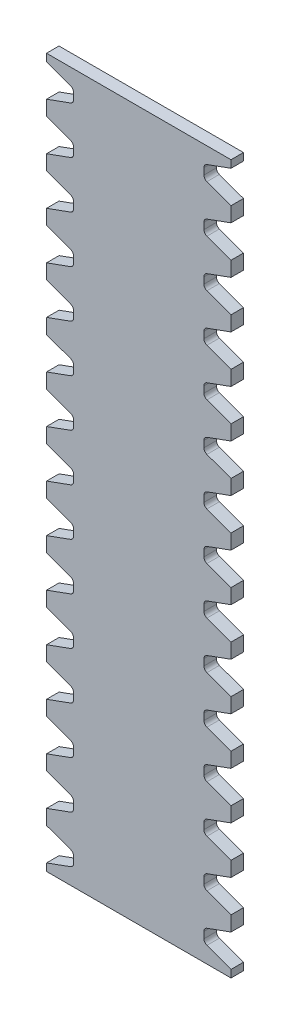
SolidWorks part; units mm, degrees
ref_plane "Front Plane" through (0, 0, 0) normal (0, 0, 1) x (1, 0, 0)
ref_plane "Top Plane" through (0, 0, 0) normal (0, 1, 0) x (1, 0, 0)
ref_plane "Right Plane" through (0, 0, 0) normal (1, 0, 0) x (0, 0, -1)
ref_axis "Axis1" through (0, -55, 0) along (0, 1, 0)
sketch "SketchCI.m_strSketchName" plane through (0, 0, 0) normal (0, 0, 1) x (1, 0, 0)
  line L0 (-7.7057, 15.1301) -> (-7.7057, -438.7728)
  line L1 (-7.7057, -438.7728) -> (51.376, -438.7728)
  line L2 (51.376, -438.7728) -> (51.376, 15.1301)
  line L3 (51.376, 15.1301) -> (-7.7057, 15.1301)
  dimension "D1" = 7.7057
  dimension "D2" = 438.7728
  dimension "D3" = 51.376
  dimension "D4" = 15.1301
extrude "ExtrudeCI" add sketch "SketchCI.m_strSketchName" along normal blind 4 and the other way blind 4
sketch "SketchToothGeartrax1Gear" plane through (0, 0, 0) normal (0, 0, 1) x (1, 0, 0)
  line L0 (-7.7057, 10.3697) -> (-7.7057, -10.3697)
  line L1 (-7.7057, -10.3697) -> (7.7308, -4.7513)
  line L2 (9.6321, -2.0359) -> (9.6321, 2.0359)
  line L3 (7.7308, 4.7513) -> (-7.7057, 10.3697)
  arc A0 (7.7308, -4.7513) -> (9.6321, -2.0359) centre (6.7425, -2.0359) ccw
  arc A1 (9.6321, 2.0359) -> (7.7308, 4.7513) centre (6.7425, 2.0359) ccw
  dimension "D1" = 5.7793
  dimension "D2" = 5.7793
  dimension "ADDENDUM" = 7.7057
  dimension "FLANKONE" = 7.1088
  dimension "FLANKONEANGLE" = 70
  dimension "DEDENDUM" = 9.6321
  dimension "FLANKTWO" = 7.1088
  dimension "FLANKTWOANGLE" = 70
extrude "ToothExtrudeCutGeartrax1Gear" cut sketch "SketchToothGeartrax1Gear" against normal blind 4 and the other way blind 4
pattern_linear "PatternGeartrax1Gear" count 15 spacing 30.2602 along (0, -1, 0) of "ToothExtrudeCutGeartrax1Gear"
sketch "AuxiliarySketchGeartrax1Gear" plane through (0, 0, 0) normal (0, 0, 1) x (1, 0, 0)
  line L0 (0, 0) -> (0, -453.9029) construction
mirror "Mirror1" about plane through (51.376, -438.7728, -4) normal (1, 0, 0) of "ExtrudeCI", "ToothExtrudeCutGeartrax1Gear", "PatternGeartrax1Gear"
